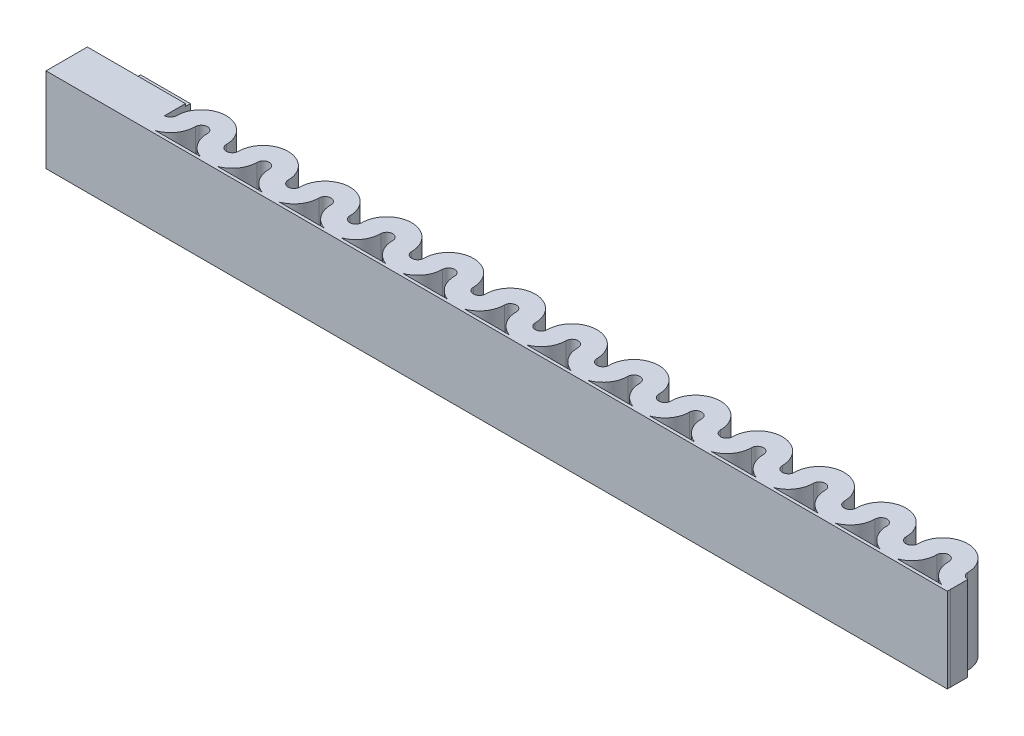
SolidWorks part; units mm, degrees
ref_plane "Front Plane" through (0, 0, 0) normal (0, 0, 1) x (1, 0, 0)
ref_plane "Top Plane" through (0, 0, 0) normal (0, 1, 0) x (1, 0, 0)
ref_plane "Right Plane" through (0, 0, 0) normal (1, 0, 0) x (0, 0, -1)
sketch "Sketch2" plane through (0, 0, 0) normal (0, 1, 0) x (1, 0, 0)
  line L1 (6.2, -1.2) -> (6.2, -1.8)
  line L2 (6.2, -4.4) -> (6.2, -5)
  line L6 (-6.2, -1.2) -> (-6.2, -1.8)
  line L8 (-6.2, -4.4) -> (-6.2, -5)
  arc A2 (1.2, 0) -> (-1.2, 0) centre (0, 0) ccw
  arc A3 (1.8, 0) -> (-1.8, 0) centre (0, 0) ccw
  arc A4 (1.2, 0) -> (6.2, -5) centre (6.2, 0) ccw
  arc A5 (1.8, 0) -> (6.2, -4.4) centre (6.2, 0) ccw
  arc A6 (5, 0) -> (6.2, -1.2) centre (6.2, 0) ccw
  arc A7 (4.4, 0) -> (6.2, -1.8) centre (6.2, 0) ccw
  arc A8 (4.4, 0) -> (-4.4, 0) centre (0, 0) ccw
  arc A9 (5, 0) -> (-5, 0) centre (0, 0) ccw
  arc A10 (-6.2, -1.8) -> (-4.4, 0) centre (-6.2, 0) ccw
  arc A11 (-6.2, -1.2) -> (-5, 0) centre (-6.2, 0) ccw
  arc A12 (-6.2, -4.4) -> (-1.8, 0) centre (-6.2, 0) ccw
  arc A13 (-6.2, -5) -> (-1.2, 0) centre (-6.2, 0) ccw
  dimension "D1" = 5
  dimension "D3" = 2.4
  dimension "D4" = 0.6
  dimension "D5" = 10
extrude "Boss-Extrude1" add sketch "Sketch2" along normal blind 15.8
sketch "Sketch5" plane through (0, 15.8, 0) normal (0, 1, 0) x (1, 0, 0)
  line L0 (-6.2, -5) -> (6.2, -5)
pattern_linear "LPattern2" count 13 spacing 12.4 along (1, 0, 0) of "Boss-Extrude1"
sketch "Sketch6" plane through (0, 15.8, 0) normal (0, 1, 0) x (1, 0, 0)
  line L0 (155, -1.2) -> (155, -5)
  line L1 (155, -5) -> (154.4, -4.8144)
  line L2 (154.4, -4.8144) -> (154.4, -1.2)
  line L3 (154.4, -1.2) -> (155, -1.2)
  dimension "D1" = 0.6
extrude "Boss-Extrude2" add sketch "Sketch6" against normal up to surface (15.8 mm away) up to face at (74.4, 0, 1.7231)
sketch "Sketch7" plane through (0, 15.8, 0) normal (0, 1, 0) x (1, 0, 0)
  line L1 (-6.2, -5) -> (-25.8889, -5)
  line L2 (-6.2, -5) -> (-6.2, 3)
  line L3 (-6.2, 3) -> (-25.8889, 3)
  line L4 (-25.8889, -5) -> (-25.8889, 3)
  dimension "D1" = 8
extrude "Boss-Extrude3" add sketch "Sketch7" against normal up to surface (15.8 mm away) up to face at (74.3911, 0, 0.1519)
sketch "Sketch8" plane through (0, 15.8, 0) normal (0, 1, 0) x (1, 0, 0)
  line L0 (-6.2, -1.8) -> (-6.2, -4.4)
  line L1 (-8, 0) -> (-10.6, 0)
  arc A1 (-8, 0) -> (-6.2, -1.8) centre (-6.2, 0) ccw
  arc A2 (-10.6, 0) -> (-6.2, -4.4) centre (-6.2, 0) ccw
extrude "Cut-Extrude1" cut sketch "Sketch8" against normal up to surface (15.8 mm away) up to face at (69.6343, 0, 0.1317)
sketch "Sketch9" plane through (-25.8889, 0, 0) normal (-1, 0, 0) x (0, 0, 1)
  line L0 (5, 0) -> (5, 15.8) construction
  line L1 (-3, 15.8) -> (5, 15.8) construction
  circle A0 centre (1, 7.9) radius 2
  dimension "D1" = 4
  dimension "D2" = 4
  dimension "D3" = 7.9
extrude "Cut-Extrude2" cut sketch "Sketch9" against normal blind 18
sketch "Sketch10" plane through (0, 0, 0) normal (0, -1, 0) x (1, 0, 0)
  line L0 (155, 5) -> (155, 1.2)
  line L1 (-25.8889, 5) -> (-6.2, 5)
  line L2 (-25.8889, 5) -> (-25.8889, -3)
  line L3 (-25.8889, -3) -> (-6.2, -3)
  line L4 (-6.2, 1.2) -> (-6.2, -3)
  arc A0 (-6.2, 5) -> (-1.2, 0) centre (-6.2, 0) cw
  arc A1 (-1.2, 0) -> (1.2, 0) centre (0, 0) ccw
  arc A2 (1.2, 0) -> (6.2, 5) centre (6.2, 0) cw
  arc A3 (11.2, 0) -> (1.2, 0) centre (6.2, 0) ccw construction
  arc A4 (6.2, 5) -> (11.2, 0) centre (6.2, 0) cw
  arc A5 (11.2, 0) -> (13.6, 0) centre (12.4, 0) ccw
  arc A7 (13.6, 0) -> (23.6, 0) centre (18.6, 0) cw
  arc A8 (23.6, 0) -> (26, 0) centre (24.8, 0) ccw
  arc A9 (26, 0) -> (36, 0) centre (31, 0) cw
  arc A10 (36, 0) -> (38.4, 0) centre (37.2, 0) ccw
  arc A11 (38.4, 0) -> (48.4, 0) centre (43.4, 0) cw
  arc A12 (48.4, 0) -> (50.8, 0) centre (49.6, 0) ccw
  arc A13 (50.8, 0) -> (60.8, 0) centre (55.8, 0) cw
  arc A14 (60.8, 0) -> (63.2, 0) centre (62, 0) ccw
  arc A15 (63.2, 0) -> (73.2, 0) centre (68.2, 0) cw
  arc A16 (73.2, 0) -> (75.6, 0) centre (74.4, 0) ccw
  arc A17 (75.6, 0) -> (85.6, 0) centre (80.6, 0) cw
  arc A18 (85.6, 0) -> (88, 0) centre (86.8, 0) ccw
  arc A19 (88, 0) -> (98, 0) centre (93, 0) cw
  arc A20 (98, 0) -> (100.4, 0) centre (99.2, 0) ccw
  arc A21 (100.4, 0) -> (110.4, 0) centre (105.4, 0) cw
  arc A22 (110.4, 0) -> (112.8, 0) centre (111.6, 0) ccw
  arc A23 (112.8, 0) -> (122.8, 0) centre (117.8, 0) cw
  arc A24 (122.8, 0) -> (125.2, 0) centre (124, 0) ccw construction
  arc A25 (122.8, 0) -> (112.8, 0) centre (117.8, 0) ccw construction
  arc A26 (122.8, 0) -> (125.2, 0) centre (124, 0) ccw
  arc A27 (125.2, 0) -> (135.2, 0) centre (130.2, 0) cw
  arc A28 (135.2, 0) -> (137.6, 0) centre (136.4, 0) ccw
  arc A29 (137.6, 0) -> (147.6, 0) centre (142.6, 0) cw
  arc A30 (147.6, 0) -> (150, 0) centre (148.8, 0) ccw
  arc A31 (150, 0) -> (155, 5) centre (155, 0) cw
  arc A32 (155, 1.2) -> (153.8, 0) centre (155, 0) ccw
  arc A33 (153.8, 0) -> (143.8, 0) centre (148.8, 0) cw
  arc A34 (143.8, 0) -> (141.4, 0) centre (142.6, 0) ccw
  arc A35 (141.4, 0) -> (131.4, 0) centre (136.4, 0) cw
  arc A36 (131.4, 0) -> (129, 0) centre (130.2, 0) ccw
  arc A37 (129, 0) -> (119, 0) centre (124, 0) cw
  arc A38 (119, 0) -> (129, 0) centre (124, 0) ccw construction
  arc A39 (119, 0) -> (116.6, 0) centre (117.8, 0) ccw
  arc A40 (116.6, 0) -> (106.6, 0) centre (111.6, 0) cw
  arc A41 (106.6, 0) -> (104.2, 0) centre (105.4, 0) ccw construction
  arc A42 (106.6, 0) -> (116.6, 0) centre (111.6, 0) ccw construction
  arc A43 (106.6, 0) -> (104.2, 0) centre (105.4, 0) ccw
  arc A44 (104.2, 0) -> (94.2, 0) centre (99.2, 0) cw
  arc A45 (94.2, 0) -> (91.8, 0) centre (93, 0) ccw
  arc A46 (91.8, 0) -> (81.8, 0) centre (86.8, 0) cw
  arc A47 (81.8, 0) -> (79.4, 0) centre (80.6, 0) ccw
  arc A48 (79.4, 0) -> (69.4, 0) centre (74.4, 0) cw
  arc A49 (69.4, 0) -> (67, 0) centre (68.2, 0) ccw
  arc A50 (67, 0) -> (57, 0) centre (62, 0) cw
  arc A51 (57, 0) -> (54.6, 0) centre (55.8, 0) ccw
  arc A52 (54.6, 0) -> (44.6, 0) centre (49.6, 0) cw
  arc A53 (44.6, 0) -> (42.2, 0) centre (43.4, 0) ccw
  arc A54 (42.2, 0) -> (32.2, 0) centre (37.2, 0) cw
  arc A55 (32.2, 0) -> (29.8, 0) centre (31, 0) ccw
  arc A56 (29.8, 0) -> (19.8, 0) centre (24.8, 0) cw
  arc A57 (19.8, 0) -> (17.4, 0) centre (18.6, 0) ccw
  arc A59 (17.4, 0) -> (7.4, 0) centre (12.4, 0) cw
  arc A60 (7.4, 0) -> (5, 0) centre (6.2, 0) ccw construction
  arc A61 (7.4, 0) -> (5, 0) centre (6.2, 0) ccw
  arc A62 (5, 0) -> (-5, 0) centre (0, 0) cw
  arc A63 (-5, 0) -> (-6.2, 1.2) centre (-6.2, 0) ccw
extrude "Boss-Extrude4" add sketch "Sketch10" along normal blind 0.6
sketch "Sketch11" plane through (0, 15.8, 0) normal (0, 1, 0) x (1, 0, 0)
  line L0 (155, -5) -> (155, -1.2)
  line L1 (-25.8889, 3) -> (-6.2, 3)
  line L2 (-25.8889, 3) -> (-25.8889, -5)
  line L3 (-25.8889, -5) -> (-6.2, -5)
  line L4 (-6.2, 3) -> (-6.2, -1.2)
  arc A0 (-6.2, -5) -> (-1.2, 0) centre (-6.2, 0) ccw
  arc A1 (-1.2, 0) -> (1.2, 0) centre (0, 0) cw
  arc A2 (1.2, 0) -> (11.2, 0) centre (6.2, 0) ccw construction
  arc A3 (1.2, 0) -> (-1.2, 0) centre (0, 0) ccw construction
  arc A4 (1.2, 0) -> (11.2, 0) centre (6.2, 0) ccw
  arc A5 (11.2, 0) -> (13.6, 0) centre (12.4, 0) cw
  arc A6 (13.6, 0) -> (23.6, 0) centre (18.6, 0) ccw
  arc A7 (23.6, 0) -> (26, 0) centre (24.8, 0) cw
  arc A8 (26, 0) -> (36, 0) centre (31, 0) ccw
  arc A9 (36, 0) -> (38.4, 0) centre (37.2, 0) cw
  arc A10 (38.4, 0) -> (48.4, 0) centre (43.4, 0) ccw
  arc A11 (38.4, 0) -> (48.4, 0) centre (43.4, 0) ccw construction
  arc A12 (48.4, 0) -> (50.8, 0) centre (49.6, 0) cw
  arc A13 (50.8, 0) -> (60.8, 0) centre (55.8, 0) ccw
  arc A14 (60.8, 0) -> (63.2, 0) centre (62, 0) cw
  arc A15 (63.2, 0) -> (73.2, 0) centre (68.2, 0) ccw
  arc A16 (73.2, 0) -> (75.6, 0) centre (74.4, 0) cw
  arc A17 (75.6, 0) -> (85.6, 0) centre (80.6, 0) ccw
  arc A18 (85.6, 0) -> (88, 0) centre (86.8, 0) cw
  arc A19 (88, 0) -> (98, 0) centre (93, 0) ccw
  arc A20 (98, 0) -> (100.4, 0) centre (99.2, 0) cw
  arc A21 (100.4, 0) -> (110.4, 0) centre (105.4, 0) ccw
  arc A22 (110.4, 0) -> (112.8, 0) centre (111.6, 0) cw
  arc A23 (112.8, 0) -> (122.8, 0) centre (117.8, 0) ccw construction
  arc A24 (112.8, 0) -> (110.4, 0) centre (111.6, 0) ccw construction
  arc A25 (112.8, 0) -> (122.8, 0) centre (117.8, 0) ccw
  arc A26 (122.8, 0) -> (125.2, 0) centre (124, 0) cw
  arc A27 (125.2, 0) -> (135.2, 0) centre (130.2, 0) ccw
  arc A28 (135.2, 0) -> (137.6, 0) centre (136.4, 0) cw
  arc A29 (137.6, 0) -> (147.6, 0) centre (142.6, 0) ccw
  arc A30 (147.6, 0) -> (150, 0) centre (148.8, 0) cw
  arc A31 (150, 0) -> (155, -5) centre (155, 0) ccw
  arc A32 (155, -1.2) -> (153.8, 0) centre (155, 0) cw
  arc A33 (153.8, 0) -> (143.8, 0) centre (148.8, 0) ccw
  arc A34 (153.8, 0) -> (143.8, 0) centre (148.8, 0) ccw construction
  arc A35 (143.8, 0) -> (141.4, 0) centre (142.6, 0) cw
  arc A36 (141.4, 0) -> (131.4, 0) centre (136.4, 0) ccw
  arc A37 (131.4, 0) -> (129, 0) centre (130.2, 0) cw
  arc A38 (129, 0) -> (131.4, 0) centre (130.2, 0) ccw construction
  arc A39 (129, 0) -> (119, 0) centre (124, 0) ccw
  arc A40 (119, 0) -> (116.6, 0) centre (117.8, 0) cw
  arc A41 (116.6, 0) -> (119, 0) centre (117.8, 0) ccw construction
  arc A42 (116.6, 0) -> (106.6, 0) centre (111.6, 0) ccw
  arc A43 (106.6, 0) -> (104.2, 0) centre (105.4, 0) cw
  arc A44 (104.2, 0) -> (94.2, 0) centre (99.2, 0) ccw
  arc A45 (94.2, 0) -> (91.8, 0) centre (93, 0) cw
  arc A46 (91.8, 0) -> (81.8, 0) centre (86.8, 0) ccw
  arc A47 (81.8, 0) -> (79.4, 0) centre (80.6, 0) cw
  arc A48 (79.4, 0) -> (69.4, 0) centre (74.4, 0) ccw
  arc A49 (69.4, 0) -> (67, 0) centre (68.2, 0) cw
  arc A50 (67, 0) -> (57, 0) centre (62, 0) ccw
  arc A51 (57, 0) -> (54.6, 0) centre (55.8, 0) cw
  arc A52 (54.6, 0) -> (44.6, 0) centre (49.6, 0) ccw
  arc A53 (44.6, 0) -> (42.2, 0) centre (43.4, 0) cw
  arc A54 (42.2, 0) -> (32.2, 0) centre (37.2, 0) ccw
  arc A55 (32.2, 0) -> (29.8, 0) centre (31, 0) cw
  arc A56 (29.8, 0) -> (19.8, 0) centre (24.8, 0) ccw construction
  arc A57 (29.8, 0) -> (32.2, 0) centre (31, 0) ccw construction
  arc A58 (29.8, 0) -> (19.8, 0) centre (24.8, 0) ccw
  arc A59 (19.8, 0) -> (17.4, 0) centre (18.6, 0) cw
  arc A60 (17.4, 0) -> (7.4, 0) centre (12.4, 0) ccw
  arc A61 (5, 0) -> (7.4, 0) centre (6.2, 0) ccw construction
  arc A62 (17.4, 0) -> (7.4, 0) centre (12.4, 0) ccw construction
  arc A63 (7.4, 0) -> (5, 0) centre (6.2, 0) cw
  arc A64 (5, 0) -> (-5, 0) centre (0, 0) ccw
  arc A65 (-5, 0) -> (-6.2, -1.2) centre (-6.2, 0) cw
extrude "Boss-Extrude5" add sketch "Sketch11" along normal blind 0.6
sketch "Sketch12" plane through (0, 16.4, 0) normal (0, 1, 0) x (1, 0, 0)
  line L0 (-25.8889, 3) -> (-25.8889, -5) construction
  line L1 (-25.8889, -4.7) -> (155.0006, -4.7)
  line L2 (-25.8889, -4.7) -> (-25.8889, -5.3)
  line L3 (-25.8889, -5.3) -> (155.0006, -5.3)
  line L4 (155.0006, -4.7) -> (155.0006, -5.3)
  arc A2 (26, 0) -> (36, 0) centre (31, 0) ccw construction
  point P12 (31, -5)
  dimension "D1" = 0.6
  dimension "D2" = 0.3
extrude "Boss-Extrude6" add sketch "Sketch12" against normal up to surface (17 mm away) up to face at (69.6343, -0.6, 0.1317)
fillet "Fillet1" radius 1 54 edges at (151.6834, 0, 2.8914) (148.8, 0, -1.8) (142.6, 0, 4.4) (136.4, 0, -1.8) (130.2, 0, 4.4) (124, 0, -1.8) (117.8, 0, 4.4) (111.6, 0, -1.8) (105.4, 0, 4.4) (99.2, 0, -1.8) (93, 0, 4.4) (86.8, 0, -1.8) (80.6, 0, 4.4) (74.4, 0, -1.8) (68.2, 0, 4.4) (62, 0, -1.8) (55.8, 0, 4.4) (-6.2, 0, 4.4) (0, 0, -1.8) (6.2, 0, 4.4) (12.4, 0, -1.8) (18.6, 0, 4.4) (24.8, 0, -1.8) (31, 0, 4.4) (37.2, 0, -1.8) (43.4, 0, 4.4) (-6.2, 0, 1.8) (0, 0, -4.4) (6.2, 0, 1.8) (12.4, 0, -4.4) (18.6, 0, 1.8) (24.8, 0, -4.4) (31, 0, 1.8) (37.2, 0, -4.4) (43.4, 0, 1.8) (153.5303, 0, 1.0392) (148.8, 0, -4.4) (142.6, 0, 1.8) (136.4, 0, -4.4) (130.2, 0, 1.8) (124, 0, -4.4) (117.8, 0, 1.8) (111.6, 0, -4.4) (105.4, 0, 1.8) (99.2, 0, -4.4) (93, 0, 1.8) (86.8, 0, -4.4) (80.6, 0, 1.8) (74.4, 0, -4.4) (68.2, 0, 1.8) (62, 0, -4.4) (55.8, 0, 1.8) (49.6, 0, -1.8) (49.6, 0, -4.4)
fillet "Fillet2" radius 1 56 edges at (62, 15.8, -4.4) (55.8, 15.8, 1.8) (49.6, 15.8, -4.4) (43.4, 15.8, 1.8) (37.2, 15.8, -4.4) (31, 15.8, 1.8) (24.8, 15.8, -4.4) (18.6, 15.8, 1.8) (12.4, 15.8, -4.4) (6.2, 15.8, 1.8) (0, 15.8, -4.4) (-6.2, 15.8, 1.8) (-9.3, 15.8, 0) (-6.2, 15.8, 4.4) (0, 15.8, -1.8) (6.2, 15.8, 4.4) (12.4, 15.8, -1.8) (18.6, 15.8, 4.4) (24.8, 15.8, -1.8) (31, 15.8, 4.4) (37.2, 15.8, -1.8) (43.4, 15.8, 4.4) (49.6, 15.8, -1.8) (55.8, 15.8, 4.4) (62, 15.8, -1.8) (68.2, 15.8, 4.4) (74.4, 15.8, -1.8) (80.6, 15.8, 4.4) (86.8, 15.8, -1.8) (93, 15.8, 4.4) (99.2, 15.8, -1.8) (105.4, 15.8, 4.4) (111.6, 15.8, -1.8) (117.8, 15.8, 4.4) (124, 15.8, -1.8) (130.2, 15.8, 4.4) (136.4, 15.8, -1.8) (142.6, 15.8, 4.4) (148.8, 15.8, -1.8) (151.6834, 15.8, 2.8914) (154.4, 15.8, 3.028) (153.5303, 15.8, 1.0392) (148.8, 15.8, -4.4) (142.6, 15.8, 1.8) (136.4, 15.8, -4.4) (130.2, 15.8, 1.8) (124, 15.8, -4.4) (117.8, 15.8, 1.8) (111.6, 15.8, -4.4) (105.4, 15.8, 1.8) (99.2, 15.8, -4.4) (93, 15.8, 1.8) (86.8, 15.8, -4.4) (80.6, 15.8, 1.8) (74.4, 15.8, -4.4) (68.2, 15.8, 1.8)
sketch "Sketch13" plane through (0, 0, -3) normal (0, 0, -1) x (-1, 0, 0)
  line L0 (6.2, 16.4) -> (6.2, -0.6) construction
  line L1 (6.2, 15.9) -> (16.2, 15.9)
  line L2 (6.2, 15.9) -> (6.2, 12.9)
  line L3 (6.2, 12.9) -> (16.2, 12.9)
  line L4 (16.2, 15.9) -> (16.2, 12.9)
  line L6 (6.2, -0.1) -> (16.2, -0.1)
  line L7 (6.2, -0.1) -> (6.2, 2.9)
  line L8 (6.2, 2.9) -> (16.2, 2.9)
  line L9 (16.2, -0.1) -> (16.2, 2.9)
  point P10 (6.2, 7.9)
  dimension "D1" = 3
  dimension "D2" = 3
  dimension "D3" = 10
  dimension "D4" = 5
  dimension "D5" = 10
  dimension "D6" = 10
extrude "Boss-Extrude7" add sketch "Sketch13" along normal blind 1
